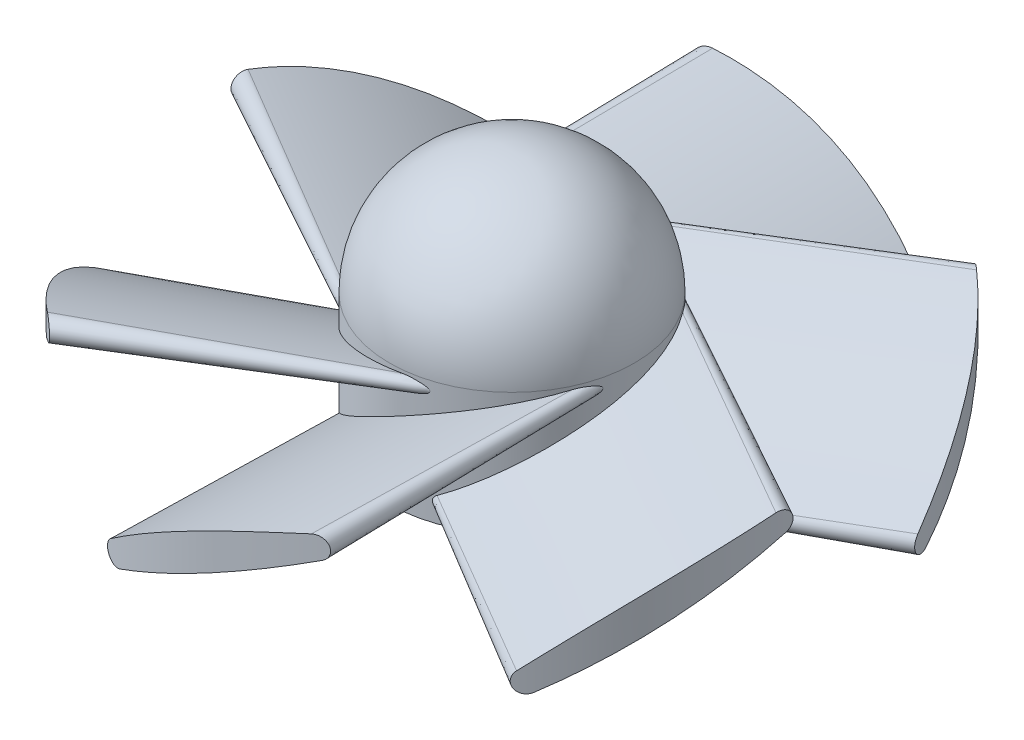
SolidWorks part; units mm, degrees
ref_plane "Plan de face" through (0, 0, 0) normal (0, 0, 1) x (1, 0, 0)
ref_plane "Plan de dessus" through (0, 0, 0) normal (0, 1, 0) x (1, 0, 0)
ref_plane "Plan de droite" through (0, 0, 0) normal (1, 0, 0) x (0, 0, -1)
sketch "Esquisse1" plane through (0, 0, 0) normal (0, 0, 1) x (1, 0, 0)
  line L0 (0, 34.9949) -> (0, -7.8007) construction
  line L1 (0, 0) -> (6.5, 0)
  line L2 (6.5, 0) -> (6.5, 6.5)
  line L3 (0, 13) -> (0, 0)
  arc A0 (6.5, 6.5) -> (0, 13) centre (0, 6.5) ccw
  dimension "D1" = 13
  dimension "D2" = 13
revolve "Révolution1" add sketch "Esquisse1" angle 360 about L0
sketch "Esquisse2" plane through (0, 0, 0) normal (0, 0, 1) x (1, 0, 0)
  line L0 (-3.8658, 0.7317) -> (6.1342, 5.7317)
  arc A0 (-4.1823, 1.2383) -> (5.9187, 6.2888) centre (14.0448, -22.5897) cw
  arc A2 (5.9187, 6.2888) -> (6.1342, 5.7317) centre (6, 6) cw
  arc A3 (-3.8658, 0.7317) -> (-4.1823, 1.2383) centre (-4, 1) cw
  dimension "D4" = 30
  dimension "D6" = 0.3
  dimension "D1" = 1
  dimension "D2" = 5
  dimension "D3" = 4
  dimension "D5" = 10
extrude "Boss.-Extru.1" add sketch "Esquisse2" along normal blind 30 draft 1 draft outward yes
ref_axis "Axe1" through (0, 26.2674, 0) along (0, -1, 0)
pattern_circular "Répétition circulaire1" count 6 over 360 about axis through (0, 26.2674, 0) along (0, -1, 0) of "Boss.-Extru.1"
sketch "Esquisse3" plane through (0, 0, 0) normal (0, 1, 0) x (1, 0, 0)
  circle A0 centre (0, 0) radius 17.5
  dimension "D1" = 35
extrude "Enlèv. mat.-Extru.1" cut sketch "Esquisse3" along normal through all flip side to cut
